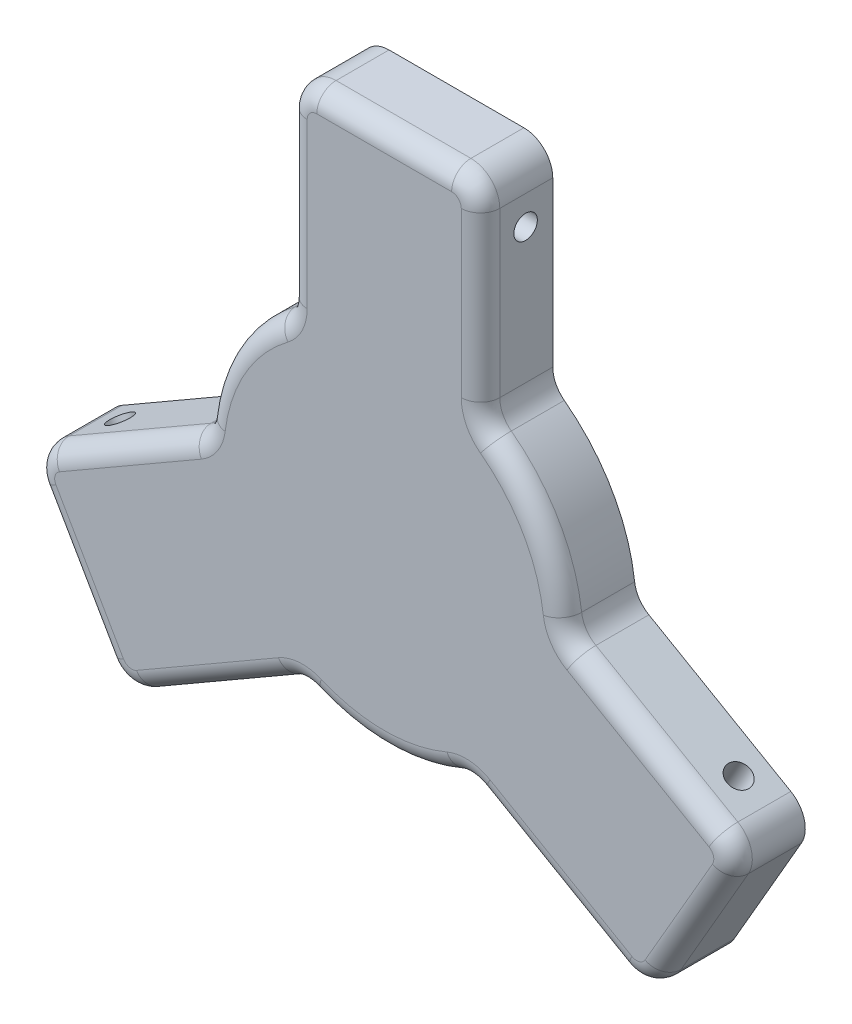
SolidWorks part; units mm, degrees
ref_plane "Front Plane" through (0, 0, 0) normal (0, 0, 1) x (1, 0, 0)
ref_plane "Top Plane" through (0, 0, 0) normal (0, 1, 0) x (1, 0, 0)
ref_plane "Right Plane" through (0, 0, 0) normal (1, 0, 0) x (0, 0, -1)
sketch "Sketch1" plane through (0, 0, 0) normal (0, 0, 1) x (1, 0, 0)
  line L0 (12.7, 21.9691) -> (12.7, 43.5864)
  line L1 (12.6758, -21.9831) -> (31.3969, -32.7917)
  line L2 (8.89, 47.3964) -> (-8.89, 47.3964)
  line L3 (-12.7, 21.9691) -> (-12.7, 43.5864)
  line L4 (25.3758, 0.014) -> (44.0969, -10.7947)
  line L5 (36.6015, -31.3972) -> (45.4915, -15.9992)
  line L6 (-25.3758, 0.014) -> (-44.0969, -10.7947)
  line L7 (-12.6758, -21.9831) -> (-31.3969, -32.7917)
  line L8 (-45.4915, -15.9992) -> (-36.6015, -31.3972)
  arc A0 (-14.2211, 18.9233) -> (-23.4986, 2.8542) centre (0, 0) ccw
  arc A1 (-9.2775, -21.7774) -> (9.2775, -21.7774) centre (0, 0) ccw
  arc A2 (23.4986, 2.8542) -> (14.2211, 18.9233) centre (0, 0) ccw
  arc A3 (-12.7, 21.9691) -> (-14.2211, 18.9233) centre (-16.51, 21.9691) cw
  arc A4 (-25.3758, 0.014) -> (-23.4986, 2.8542) centre (-27.2808, 3.3135) ccw
  arc A5 (-44.0969, -10.7947) -> (-45.4915, -15.9992) centre (-42.1919, -14.0942) ccw
  arc A6 (-31.3969, -32.7917) -> (-36.6015, -31.3972) centre (-33.3019, -29.4922) cw
  arc A7 (-12.6758, -21.9831) -> (-9.2775, -21.7774) centre (-10.7708, -25.2826) cw
  arc A8 (12.6758, -21.9831) -> (9.2775, -21.7774) centre (10.7708, -25.2826) ccw
  arc A9 (31.3969, -32.7917) -> (36.6015, -31.3972) centre (33.3019, -29.4922) ccw
  arc A10 (44.0969, -10.7947) -> (45.4915, -15.9992) centre (42.1919, -14.0942) cw
  arc A11 (25.3758, 0.014) -> (23.4986, 2.8542) centre (27.2808, 3.3135) cw
  arc A12 (12.7, 21.9691) -> (14.2211, 18.9233) centre (16.51, 21.9691) ccw
  arc A13 (12.7, 43.5864) -> (8.89, 47.3964) centre (8.89, 43.5864) ccw
  arc A14 (-8.89, 47.3964) -> (-12.7, 43.5864) centre (-8.89, 43.5864) ccw
  point P17 (0, 0)
  point P37 (12.7, 47.3964)
  point P40 (-12.7, 47.3964)
  dimension "D1" = 47.3964
  dimension "D5" = 3.81
  dimension "D2" = 25.4
  dimension "D3" = 12.7
  dimension "D4" = 3
extrude "Boss-Extrude1" add sketch "Sketch1" along normal blind 9.525
fillet "Fillet1" radius 2.54 24 edges at (-11.5841, 46.2805, 9.525) (0, 47.3964, 9.525) (11.5841, 46.2805, 9.525) (12.7, 32.7777, 9.525) (13.1014, 20.2668, 9.525) (20.4999, 11.8356, 9.525) (24.1023, 1.2127, 9.525) (34.7364, -5.3903, 9.525) (45.8721, -13.1081, 9.525) (41.0465, -23.6982, 9.525) (34.288, -33.1723, 9.525) (22.0364, -27.3874, 9.525) (11.0009, -21.4796, 9.525) (0, -23.6713, 9.525) (-11.0009, -21.4796, 9.525) (-22.0364, -27.3874, 9.525) (-34.288, -33.1723, 9.525) (-41.0465, -23.6982, 9.525) (-45.8721, -13.1081, 9.525) (-34.7364, -5.3903, 9.525) (-24.1023, 1.2127, 9.525) (-20.4999, 11.8356, 9.525) (-13.1014, 20.2668, 9.525) (-12.7, 32.7777, 9.525)
sketch "Sketch3" plane through (-6.35, -10.9985, 0) normal (-0.5, -0.866, 0) x (0.866, -0.5, 0)
  circle A0 centre (39.7764, 3.582) radius 1.55 construction
  circle A1 centre (39.7764, 3.582) radius 1.55
extrude "Cut-Extrude2" cut sketch "Sketch3" against normal blind 5.08 contours A1
sketch "Sketch4" plane through (6.35, 10.9985, 0) normal (0.5, 0.866, 0) x (0.866, -0.5, 0)
  circle A0 centre (39.7764, -3.582) radius 1.55 construction
  circle A1 centre (39.7764, -3.582) radius 1.55
extrude "Cut-Extrude3" cut sketch "Sketch4" against normal blind 5.08
ref_axis "Axis3" through (0, 0, 0) along (0, 0, -1)
pattern_circular "CirPattern2" count 3 over 360 about axis through (0, 0, 0) along (0, 0, -1) of "Cut-Extrude2", "Cut-Extrude3"
